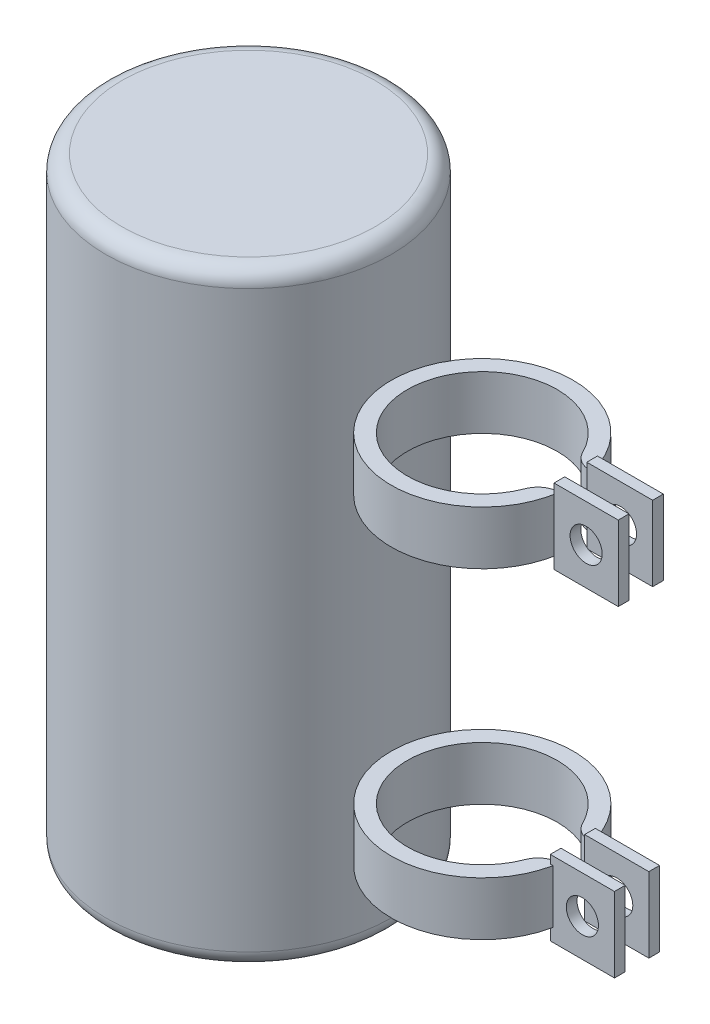
SolidWorks part; units mm, degrees
material "1060 Alloy"
ref_plane "Front Plane" through (0, 0, 0) normal (0, 0, 1) x (1, 0, 0)
ref_plane "Top Plane" through (0, 0, 0) normal (0, 1, 0) x (1, 0, 0)
ref_plane "Right Plane" through (0, 0, 0) normal (1, 0, 0) x (0, 0, -1)
sketch "Sketch1" plane through (0, 0, 0) normal (0, 1, 0) x (1, 0, 0)
  circle A0 centre (0, 0) radius 13.3333
  dimension "D1" = 26.6667
extrude "Boss-Extrude1" add sketch "Sketch1" along normal blind 56.6667
shell "Shell1" thickness 1.5
sketch "Sketch4" plane through (0, 1.5, 0) normal (0, 1, 0) x (1, 0, 0)
  line L0 (-8.2442, -8.4889) -> (8.2442, -8.4889)
  arc A0 (8.2442, -8.4889) -> (-8.2442, -8.4889) centre (0, 0) ccw
extrude "Boss-Extrude2" add sketch "Sketch4" along normal mid plane 1.5 from offset 25
fillet "Fillet1" radius 1.5 6 edges at (0, 56.6667, 13.3333) (0, 1.5, 11.8333) (0, 0, 13.3333) (0, 55.1667, 11.8333) (0, 25.75, -11.8333) (0, 27.25, -11.8333)
sketch "Sketch5" plane through (0, 0, 0) normal (0, 1, 0) x (1, 0, 0)
  circle A1 centre (21.8333, 0) radius 8.5 construction
  circle A2 centre (0, 0) radius 13.3333 construction
  arc A3 (30.0947, 2) -> (30.2467, -1.2103) centre (21.8333, 0) ccw
  arc A4 (28.1076, 3.1037) -> (28.3729, -2.4969) centre (21.8333, 0) ccw
  arc A5 (28.6368, 1.6471) -> (28.762, -0.9967) centre (21.8333, 0) ccw construction
  arc A6 (28.1076, 3.1037) -> (30.0947, 2) centre (29.9003, 3.9905) ccw
  arc A7 (28.3729, -2.4969) -> (30.2467, -1.2103) centre (30.2413, -3.2103) cw
  point P0 (30.0947, 2)
  point P1 (30.0947, -2)
  point P4 (13.3333, 0)
  point P5 (13.3333, 0)
  point P6 (30.3333, 0)
  dimension "D1" = 17
  dimension "D6" = 2
  dimension "D2" = 2
  dimension "D3" = 2
  dimension "D4" = 1.5
extrude "Boss-Extrude3" add sketch "Sketch5" along normal blind 5 from offset 40 separate body contours A3 A7 A4 A6
extrude "Boss-Extrude4" add sketch "Sketch5<3>" along normal blind 5 from offset 10 separate body
sketch "Sketch5<3>" plane through (0, 0, 0) normal (0, 1, 0) x (1, 0, 0) same geometry as "Sketch5"
ref_plane "Plane1" through (0, 0, 1.2103) normal (0, 0, 1) x (0, -1, 0)
sketch "Sketch6" plane through (0, 0, 1.2103) normal (0, 0, 1) x (0, -1, 0)
  line L0 (-46, 30.2467) -> (-46, 36.2467)
  line L2 (-46, 36.2467) -> (-39, 36.2467)
  line L3 (-39, 36.2467) -> (-39, 30.2467)
  line L4 (-39, 30.2467) -> (-39, 36.2467)
  line L5 (-46, 30.2467) -> (-39, 30.2467)
  line L6 (-45, 30.2467) -> (-40, 30.2467) construction
  point P10 (-42.5, 36.2467)
  dimension "D1" = 6
  dimension "D2" = 7
extrude "Boss-Extrude5" add sketch "Sketch6" against normal mid plane 1 separate body contours L0 L5 L3 L2 region at (33.2467, 42.5, 1.2103)
ref_plane "Plane2" through (0, 0, -2) normal (0, 0, 1) x (0, -1, 0)
sketch "Sketch7" plane through (0, 0, -2) normal (0, 0, 1) x (0, -1, 0)
  line L3 (-46, 36.2467) -> (-39, 36.2467)
  line L4 (-39, 36.2467) -> (-39, 30.0947)
  line L5 (-39, 30.0947) -> (-46, 30.0947)
  line L7 (-46, 30.0947) -> (-46, 36.2467)
  line L9 (-45, 30.0947) -> (-40, 30.0947) construction
  line L10 (-45, 30.0947) -> (-40, 30.0947) construction
extrude "Boss-Extrude6" add sketch "Sketch7" along normal mid plane 1 separate body
sketch "Sketch10" plane through (0, 0, 1.2103) normal (0, 0, 1) x (0, -1, 0)
  line L0 (-46, 36.2467) -> (-39, 36.2467) construction
  line L1 (-39, 36.2467) -> (-39, 30.2467) construction
  circle A0 centre (-42.5, 33.2467) radius 1.5
  point P2 (-42.5, 36.2467)
  point P3 (-39, 33.2467)
  dimension "D1" = 3
extrude "Cut-Extrude1" cut sketch "Sketch10" against normal through all both and the other way through all
ref_plane "Plane4" through (0, 0, 1.2103) normal (0, 0, 1) x (0, -1, 0)
ref_plane "Plane5" through (0, 0, -2) normal (0, 0, 1) x (0, -1, 0)
sketch "Sketch14" plane through (0, 1.5, 0) normal (0, 1, 0) x (1, 0, 0)
  circle A0 centre (0, -9.1222) radius 2.5
  dimension "D1" = 5
extrude "Cut-Extrude3" cut sketch "Sketch14" against normal through all from surface contours A0 starting at face at (0, 25.75, -0.9222)
sketch "Sketch17" plane through (0, 0, 1.2103) normal (0, 0, 1) x (0, -1, 0)
  line L0 (-15.7788, 29.8944) -> (-8.7788, 29.8944)
  line L1 (-8.7788, 29.8944) -> (-8.7788, 35.8944)
  line L2 (-8.7788, 35.8944) -> (-15.7788, 35.8944)
  line L3 (-15.7788, 35.8944) -> (-15.7788, 29.8944)
  dimension "D1" = 7
  dimension "D2" = 6
extrude "Boss-Extrude7" add sketch "Sketch17" along normal mid plane 1
sketch "Sketch18" plane through (0, 0, -2) normal (0, 0, 1) x (0, -1, 0)
  line L0 (-15.7788, 35.8944) -> (-15.7788, 29.8944)
  line L2 (-15.7788, 35.8944) -> (-15.7788, 29.8944) construction
  line L3 (-15.7788, 29.8944) -> (-8.7788, 29.8944)
  line L4 (-8.7788, 29.8944) -> (-8.7788, 35.8944)
  line L5 (-8.7788, 35.8944) -> (-15.7788, 35.8944)
  line L6 (-15.7788, 29.8944) -> (-8.7788, 29.8944) construction
extrude "Boss-Extrude8" add sketch "Sketch18" along normal mid plane 1
sketch "Sketch19" plane through (0, 0, 1.7103) normal (0, 0, 1) x (1, 0, 0)
  line L0 (35.8944, 15.7788) -> (29.8944, 15.7788) construction
  line L1 (35.8944, 8.7788) -> (35.8944, 15.7788) construction
  circle A0 centre (32.8944, 12.2788) radius 1.5
  point P0 (32.8944, 15.7788)
  point P1 (35.8944, 12.2788)
  dimension "D1" = 3
extrude "Cut-Extrude4" cut sketch "Sketch19" against normal through all both and the other way through all
